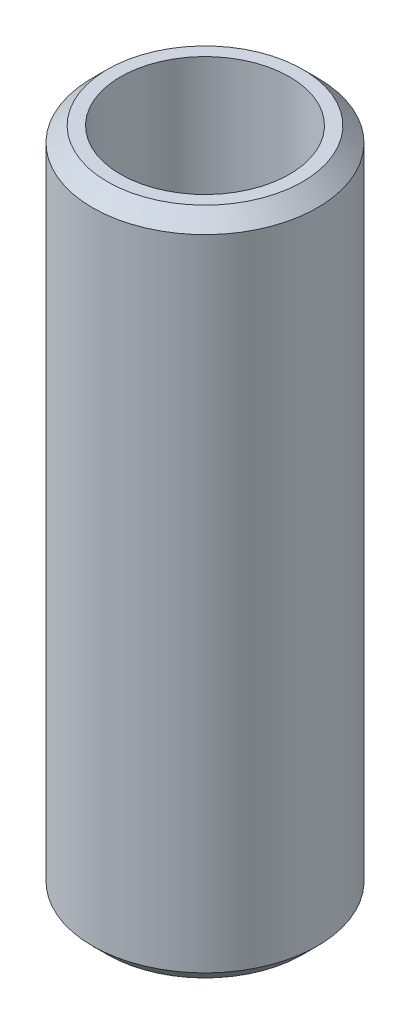
SolidWorks part; units mm, degrees
ref_plane "Front Plane" through (0, 0, 0) normal (0, 0, 1) x (1, 0, 0)
ref_plane "Top Plane" through (0, 0, 0) normal (0, 1, 0) x (1, 0, 0)
ref_plane "Right Plane" through (0, 0, 0) normal (1, 0, 0) x (0, 0, -1)
sketch "Sketch1" plane through (0, 0, 0) normal (0, 1, 0) x (1, 0, 0)
  circle A0 centre (0, 0) radius 35
  dimension "SHAFT_OD" = 70
extrude "Boss-Extrude1" add sketch "Sketch1" along normal blind 208.2985
sketch "Sketch2" plane through (0, 0, 0) normal (0, 1, 0) x (1, 0, 0)
  circle A0 centre (0, 0) radius 26.2994
  dimension "BORE_D" = 52.5988
extrude "Cut-Extrude1" cut sketch "Sketch2" along normal through all
chamfer "Chamfer1" distance 4.6552 angle 45 2 edges at (0, 208.2985, 35) (0, 0, 35)
